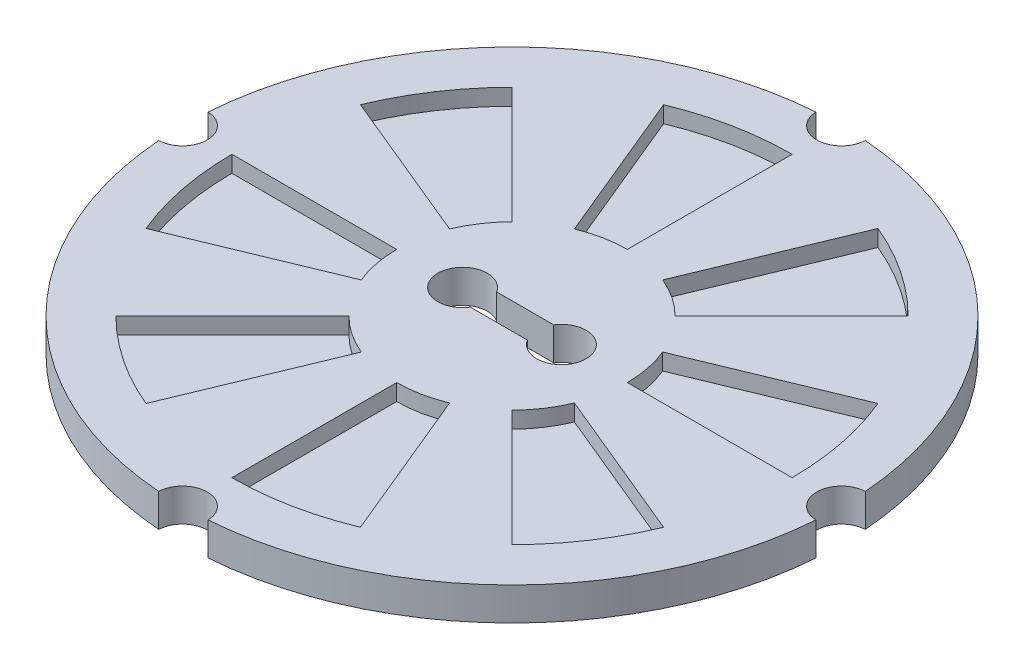
SolidWorks part; units mm, degrees
ref_plane "Front Plane" through (0, 0, 0) normal (0, 0, 1) x (1, 0, 0)
ref_plane "Top Plane" through (0, 0, 0) normal (0, 1, 0) x (1, 0, 0)
ref_plane "Right Plane" through (0, 0, 0) normal (1, 0, 0) x (0, 0, -1)
sketch "Sketch1" plane through (0, 0, 0) normal (0, 1, 0) x (1, 0, 0)
  circle A0 centre (0, 0) radius 127
  dimension "D1" = 254
extrude "Boss-Extrude1" add sketch "Sketch1" along normal blind 12.7
sketch "Sketch2" plane through (0, 12.7, 0) normal (0, 1, 0) x (1, 0, 0)
  line L0 (41.0664, 17.0103) -> (99.7328, 41.3107)
  line L1 (44.45, 0) -> (107.95, 0)
  line L2 (41.0664, -17.0103) -> (99.7328, -41.3107)
  line L3 (31.4309, -31.4309) -> (76.3322, -76.3322)
  line L4 (17.0103, -41.0664) -> (41.3107, -99.7328)
  line L5 (0, -44.45) -> (0, -107.95)
  line L6 (-17.0103, -41.0664) -> (-41.3107, -99.7328)
  line L7 (-31.4309, -31.4309) -> (-76.3322, -76.3322)
  line L8 (-41.0664, -17.0103) -> (-99.7328, -41.3107)
  line L9 (-44.45, 0) -> (-107.95, 0)
  line L10 (-41.0664, 17.0103) -> (-99.7328, 41.3107)
  line L11 (-31.4309, 31.4309) -> (-76.3322, 76.3322)
  line L12 (-17.0103, 41.0664) -> (-41.3107, 99.7328)
  line L13 (0, 44.45) -> (0, 107.95)
  line L14 (17.0103, 41.0664) -> (41.3107, 99.7328)
  line L15 (31.4309, 31.4309) -> (76.3322, 76.3322)
  line L16 (0, 5.08) -> (0, 25.4) construction
  line L17 (10.9928, -5.08) -> (-10.9928, -5.08)
  line L18 (10.9928, 5.08) -> (-10.9928, 5.08)
  arc A0 (107.95, 0) -> (99.7328, 41.3107) centre (0, 0) ccw
  arc A1 (44.45, 0) -> (41.0664, 17.0103) centre (0, 0) ccw
  arc A2 (31.4309, -31.4309) -> (41.0664, -17.0103) centre (0, 0) ccw
  arc A3 (76.3322, -76.3322) -> (99.7328, -41.3107) centre (0, 0) ccw
  arc A4 (0, -44.45) -> (17.0103, -41.0664) centre (0, 0) ccw
  arc A5 (0, -107.95) -> (41.3107, -99.7328) centre (0, 0) ccw
  arc A6 (-31.4309, -31.4309) -> (-17.0103, -41.0664) centre (0, 0) ccw
  arc A7 (-76.3322, -76.3322) -> (-41.3107, -99.7328) centre (0, 0) ccw
  arc A8 (-44.45, 0) -> (-41.0664, -17.0103) centre (0, 0) ccw
  arc A9 (-107.95, 0) -> (-99.7328, -41.3107) centre (0, 0) ccw
  arc A10 (-31.4309, 31.4309) -> (-41.0664, 17.0103) centre (0, 0) ccw
  arc A11 (-76.3322, 76.3322) -> (-99.7328, 41.3107) centre (0, 0) ccw
  arc A12 (0, 44.45) -> (-17.0103, 41.0664) centre (0, 0) ccw
  arc A13 (0, 107.95) -> (-41.3107, 99.7328) centre (0, 0) ccw
  arc A14 (31.4309, 31.4309) -> (17.0103, 41.0664) centre (0, 0) ccw
  arc A15 (76.3322, 76.3322) -> (41.3107, 99.7328) centre (0, 0) ccw
  arc A16 (10.9928, -5.08) -> (10.9928, 5.08) centre (19.05, 0) ccw
  arc A17 (-10.9928, -5.08) -> (-10.9928, 5.08) centre (-19.05, 0) cw
  circle A18 centre (0, 127) radius 9.525
  circle A19 centre (0, 0) radius 127 construction
  circle A20 centre (127, 0) radius 9.525
  circle A21 centre (0, -127) radius 9.525
  circle A22 centre (-127, 0) radius 9.525
  point P42 (0, -5.08)
  point P45 (0, 5.08)
  point P46 (-156.7853, -2.2002)
  point P47 (0, 0)
  circle M5 centre (0, 0) radius 127
  dimension "D1" = 215.9
  dimension "D4" = 88.9
  dimension "D6" = 19.05
  dimension "D10" = 19.05
  dimension "D2" = 8
  dimension "D3" = 22.5
  dimension "D5" = 25.4
  dimension "D7" = 5.08
  dimension "D8" = 5.08
  dimension "D9" = 19.05
  dimension "D11" = 4
extrude "Cut-Extrude1" cut sketch "Sketch2" against normal blind 6.35 contours L11 A11 L10 A10 | L9 A9 L8 A8 | L7 A7 L6 A6 | L5 A5 L4 A4 | L3 A3 L2 A2 | A1 L1 A0 L0 | L15 A15 L14 A14 | L13 A13 L12 A12 region at (78.5538, 12.7, -15.6253) region at (66.5947, 12.7, 44.4972) region at (15.6253, 12.7, 78.5538) region at (-44.4972, 12.7, 66.5947) region at (-78.5538, 12.7, 15.6253) region at (-66.5947, 12.7, -44.4972) region at (-15.6253, 12.7, -78.5538) region at (44.4972, 12.7, -66.5947)
extrude "Cut-Extrude2" cut sketch "Sketch2<3>" against normal through all contours A17 L17 A16 L18 | A21 M5 | A18 M5 | A20 M5 | A22 M5 | A22 region at (0, 12.7, 0) region at (0, 12.7, -122.8938) region at (-122.8938, 12.7, 0) region at (122.8938, 12.7, 0) region at (0, 12.7, 122.8938)
sketch "Sketch2<3>" plane through (0, 12.7, 0) normal (0, 1, 0) x (1, 0, 0) same geometry as "Sketch2"
